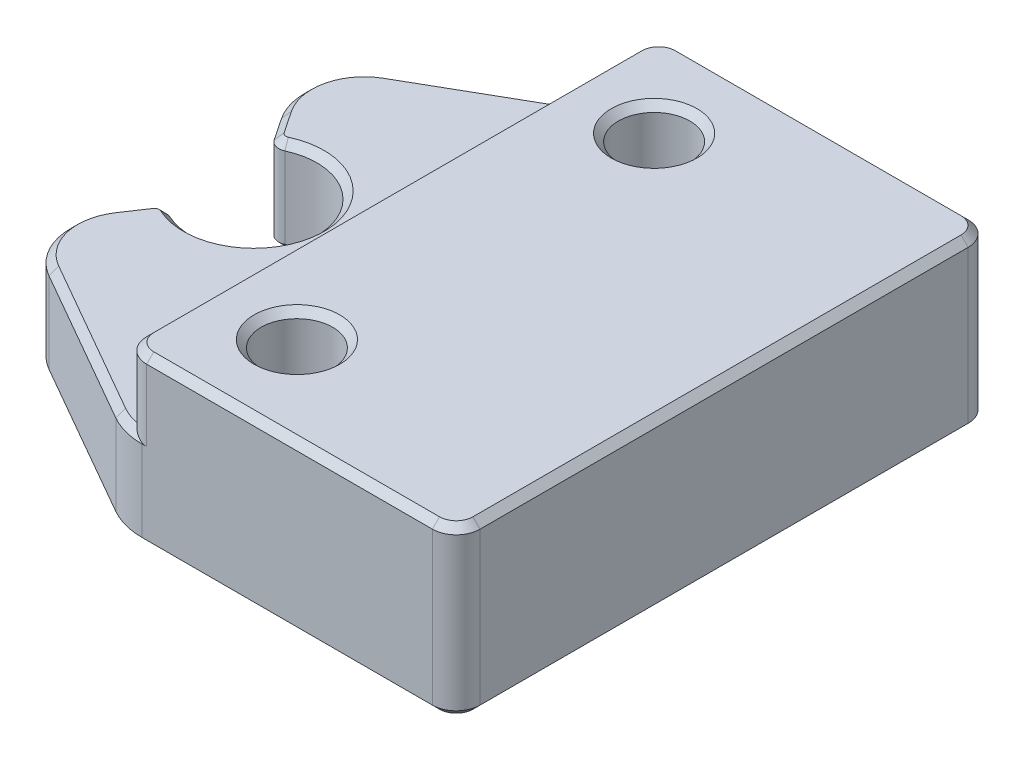
SolidWorks part; units mm, degrees
ref_plane "Front Plane" through (0, 0, 0) normal (0, 0, 1) x (1, 0, 0)
ref_plane "Top Plane" through (0, 0, 0) normal (0, 1, 0) x (1, 0, 0)
ref_plane "Right Plane" through (0, 0, 0) normal (1, 0, 0) x (0, 0, -1)
sketch "Sketch1" plane through (0, 0, 0) normal (0, 1, 0) x (1, 0, 0)
  line L0 (0, 0) -> (-3.8478, 5.75)
  line L1 (0, 0) -> (-5.65, 0) construction
  line L2 (0, 0) -> (-3.8478, -5.75)
  line L3 (9.31, -7.5) -> (9.31, 7.5) construction
  line L4 (6.75, 10.25) -> (22.05, 10.25) construction
  line L5 (6.75, 10.25) -> (6.75, -10.25) construction
  line L6 (6.75, -10.25) -> (22.05, -10.25) construction
  line L7 (22.05, 10.25) -> (22.05, -10.25) construction
  line L8 (-5.75, -5.75) -> (5.75, -5.75)
  line L9 (-5.75, -5.75) -> (-5.75, 5.75)
  line L10 (-5.75, 5.75) -> (5.75, 5.75)
  line L11 (5.75, -5.75) -> (5.75, 5.75)
  line L12 (-5.75, -5.75) -> (5.75, 5.75) construction
  line L13 (-5.75, 5.75) -> (5.75, -5.75) construction
  line L14 (23.05, 11.25) -> (23.05, -11.25)
  line L15 (5.75, -11.25) -> (23.05, -11.25)
  line L16 (5.75, 11.25) -> (5.75, -11.25)
  line L17 (5.75, 11.25) -> (23.05, 11.25)
  line L18 (19.75, 11.25) -> (19.75, -11.25)
  line L19 (-3.8478, 5.75) -> (5.75, 11.25)
  line L20 (-3.8478, -5.75) -> (5.75, -11.25)
  circle A0 centre (0, 0) radius 2.65
  circle A1 centre (0, 0) radius 5.65
  circle A2 centre (9.31, 7.5) radius 1.5
  circle A3 centre (9.31, -7.5) radius 1.5
  point P11 (6.75, 0)
  point P20 (9.31, 0)
  dimension "D1" = 5.3
  dimension "D8" = 3
  dimension "D3" = 56.21
  dimension "D4" = 20.5
  dimension "D5" = 15.3
  dimension "D6" = 5.75
  dimension "D7" = 15
  dimension "D9" = 2.56
  dimension "D10" = 1
  dimension "D12" = 13
  dimension "D13" = 56.21
  dimension "D2" = 3
  dimension "D11" = 1
extrude "Boss-Extrude1" add sketch "Sketch1" along normal blind 4 contours L8 L20 L16 | L2 A1 L0 A0 | A1 L2 L8 L11 L10 L0 | L19 L10 L16 | L18 L17 L16 L11 L15 A3 A2 region at (-2.189, 0, -3.5286) region at (-3.3706, 0, -5.3061) region at (2.5507, 0, -7.5833) region at (2.5507, 0, 7.5833) region at (12.9116, 0, 0)
extrude "Boss-Extrude2" add sketch "Sketch1<3>" along normal blind 4 from offset 3 contours L18 L17 L16 L11 L15 A3 A2 region at (12.9116, 0, 0)
sketch "Sketch1<3>" plane through (0, 0, 0) normal (0, 1, 0) x (1, 0, 0) same geometry as "Sketch1"
fillet "Fillet1" radius 0.5 1 edges at (-1.4738, 2, 2.2024)
fillet "Fillet2" radius 2.5 1 edges at (-3.8478, 2, 5.75)
fillet "Fillet3" radius 0.5 1 edges at (-1.4738, 2, -2.2024)
fillet "Fillet4" radius 2.5 1 edges at (-3.8478, 2, -5.75)
fillet "Fillet5" radius 1 1 edges at (19.75, 3.5, 11.25)
fillet "Fillet6" radius 1 1 edges at (19.75, 3.5, -11.25)
fillet "Fillet9" radius 1 2 edges at (5.75, 5.5, -11.25) (5.75, 5.5, 11.25) tangent propagation no
fillet "Fillet10" radius 3 2 edges at (5.75, 2, -11.25) (5.75, 2, 11.25)
chamfer "Chamfer1" distance 0.3 angle 45 41 edges at (9.31, 0, 9) (9.31, 7, 9) (9.31, 0, -6) (9.31, 7, -6) (-2.0436, 0, -3.0538) (-1.4501, 0, -2.3816) (-2.7138, 0, -5.4841) (2.65, 0, 0) (1.7671, 0, -8.9676) (-1.4501, 0, 2.3816) (5.7769, 0, -11.149) (-2.0436, 0, 3.0538) (12.6493, 0, -11.25) (-2.7138, 0, 5.4841) (19.4571, 0, -10.9571) (1.7671, 0, 8.9676) (19.75, 0, 0) (5.7769, 0, 11.149) (19.4571, 0, 10.9571) (12.6493, 0, 11.25) (6.6493, 4, 11.25) (6.6493, 4, -11.25) (5.7769, 4, 11.149) (5.7769, 4, -11.149) (1.7671, 4, 8.9676) (1.7671, 4, -8.9676) (-2.7138, 4, 5.4841) (-2.7138, 4, -5.4841) (-2.0436, 4, 3.0538) (-2.0436, 4, -3.0538) (-1.4501, 4, 2.3816) (-1.4501, 4, -2.3816) (2.65, 4, 0) (19.75, 7, 0) (19.4571, 7, -10.9571) (19.4571, 7, 10.9571) (12.75, 7, -11.25) (12.75, 7, 11.25) (6.0429, 7, -10.9571) (6.0429, 7, 10.9571) (5.75, 7, 0)
